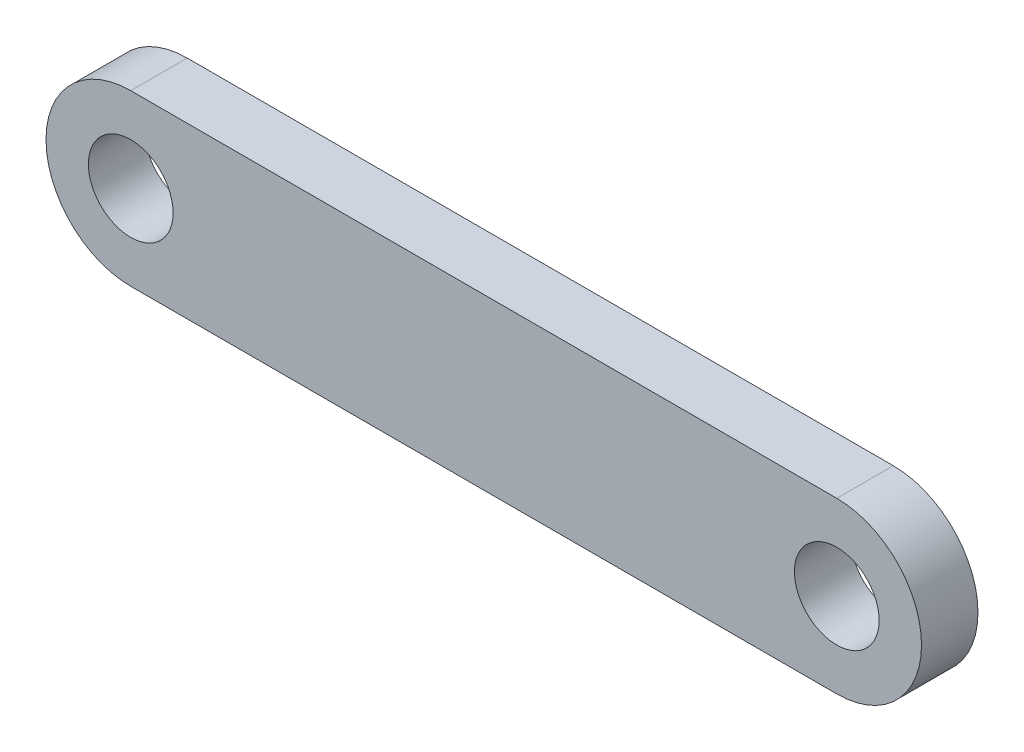
SolidWorks part; units mm, degrees
ref_plane "Plan de face" through (0, 0, 0) normal (0, 0, 1) x (1, 0, 0)
ref_plane "Plan de dessus" through (0, 0, 0) normal (0, 1, 0) x (1, 0, 0)
ref_plane "Plan de droite" through (0, 0, 0) normal (1, 0, 0) x (0, 0, -1)
sketch "Esquisse1" plane through (0, 0, 0) normal (0, 0, 1) x (1, 0, 0)
  line L0 (0, 3) -> (25, 3)
  line L3 (25, -3) -> (0, -3)
  arc A2 (0, 3) -> (0, -3) centre (0, 0) ccw
  arc A3 (25, 3) -> (25, -3) centre (25, 0) cw
  circle A4 centre (0, 0) radius 1.5
  circle A5 centre (25, 0) radius 1.5
  dimension "D1" = 3
  dimension "D2" = 3
  dimension "D3" = 3
  dimension "D5" = 3
  dimension "D4" = 25
extrude "Boss.-Extru.1" add sketch "Esquisse1" along normal blind 4 contours A3 L0 A2 L3 A5 | A4 region at (12.5, 0, 0)
extrude "Enlèv. mat.-Extru.1" cut sketch "Esquisse1<4>" along normal blind 2 contours A4 region at (12.5, 0, 0)
sketch "Esquisse1<4>" plane through (0, 0, 0) normal (0, 0, 1) x (1, 0, 0) same geometry as "Esquisse1"
